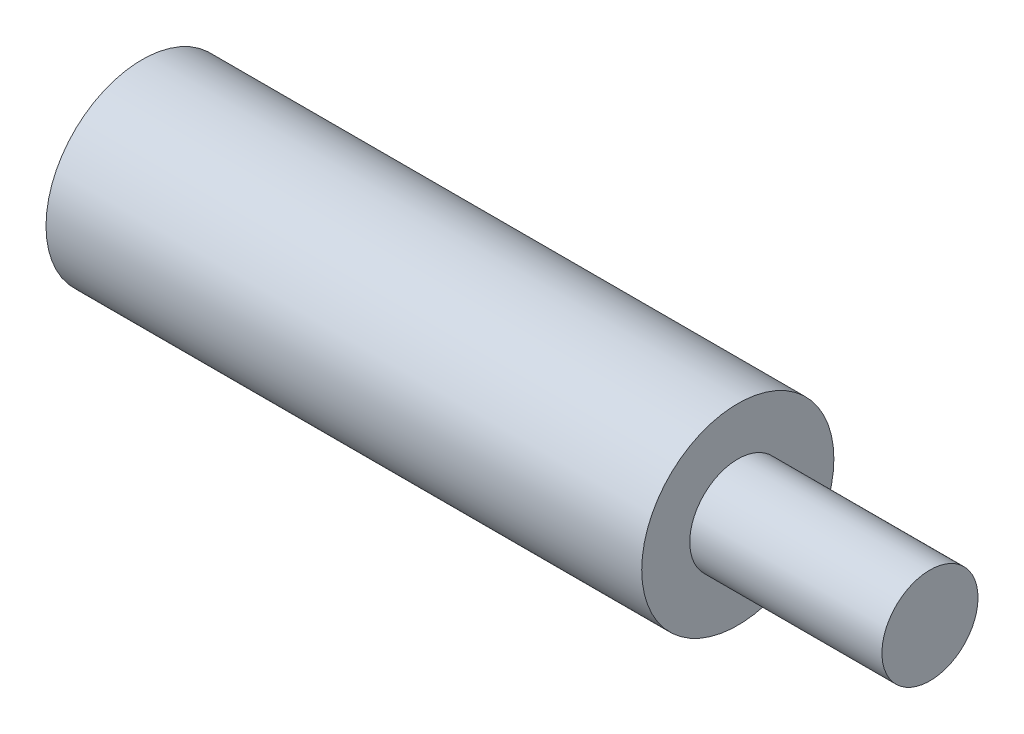
SolidWorks part; units mm, degrees
ref_plane "Ebene vorne" through (0, 0, 0) normal (0, 0, 1) x (1, 0, 0)
ref_plane "Ebene oben" through (0, 0, 0) normal (0, 1, 0) x (1, 0, 0)
ref_plane "Ebene rechts" through (0, 0, 0) normal (1, 0, 0) x (0, 0, -1)
sketch "Skizze1" plane through (0, 0, 0) normal (0, 0, 1) x (1, 0, 0)
  line L0 (0, 3) -> (18.6, 3)
  line L1 (18.6, 3) -> (18.6, 1.5)
  line L2 (18.6, 1.5) -> (24.6, 1.5)
  line L3 (24.6, 1.5) -> (24.6, 0)
  line L4 (24.6, 0) -> (0, 0)
  line L5 (0, 0) -> (0, 3)
  dimension "D1" = 18.6
  dimension "D2" = 6
  dimension "D3" = 3
  dimension "D4" = 1.5
revolve "Rotation1" add sketch "Skizze1" angle 360 about L4
cosmetic thread "Gewindedarstellung1" parameters "D2"=2.439
hole_wizard "M3 Gewindebohrung1" positions "Skizze3" profile "Skizze2" tap size "M3" standard "DIN"
sketch "Skizze3" plane through (0, 0, 0) normal (-1, 0, 0) x (0, 0, 1)
  point P0 (0, 0)
sketch "Skizze2" plane through (0, 0, 0) normal (0, 1, 0) x (0, 0, 1)
  line L0 (0, 0) -> (0, 5.7511)
  line L1 (0, 5.7511) -> (1.25, 5)
  line L2 (1.25, 5) -> (1.25, 0)
  line L5 (1.25, 0) -> (0, 0)
  line L10 (0, 5.7511) -> (-1.25, 5) construction
  line L11 (0, -6.35) -> (0, 107.95) construction
  dimension "Bohrerdurchmesser" = 2.5
  dimension "Bohrungstiefe" = 5
  dimension "Spitzenwinkel" = 118
cosmetic thread "Bohrungsgewinde1"
